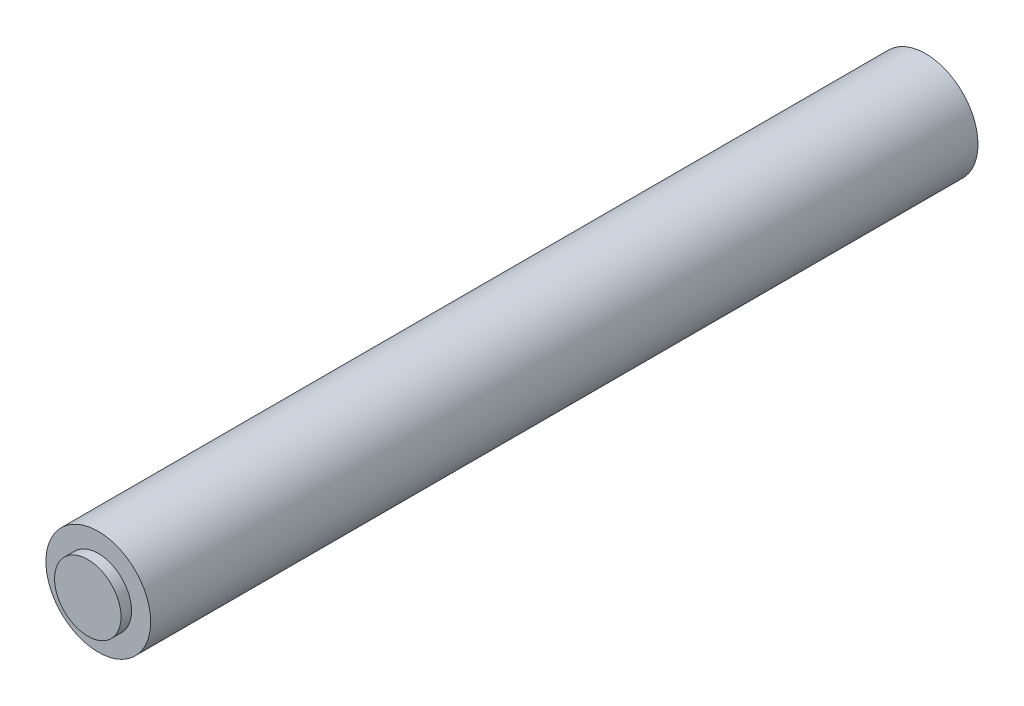
SolidWorks part; units mm, degrees
ref_plane "Front Plane" through (0, 0, 0) normal (0, 0, 1) x (1, 0, 0)
ref_plane "Top Plane" through (0, 0, 0) normal (0, 1, 0) x (1, 0, 0)
ref_plane "Right Plane" through (0, 0, 0) normal (1, 0, 0) x (0, 0, -1)
sketch "Sketch1" plane through (0, 0, 0) normal (0, 0, 1) x (1, 0, 0)
  circle A0 centre (0, 0) radius 3.175
  dimension "D1" = 6.35
extrude "Boss-Extrude1" add sketch "Sketch1" along normal mid plane 81
sketch "Sketch2" plane through (0, 0, 0) normal (0, 0, 1) x (1, 0, 0)
  circle A0 centre (0, 0) radius 5
  dimension "D1" = 10
extrude "Boss-Extrude2" add sketch "Sketch2" along normal mid plane 79 separate body
